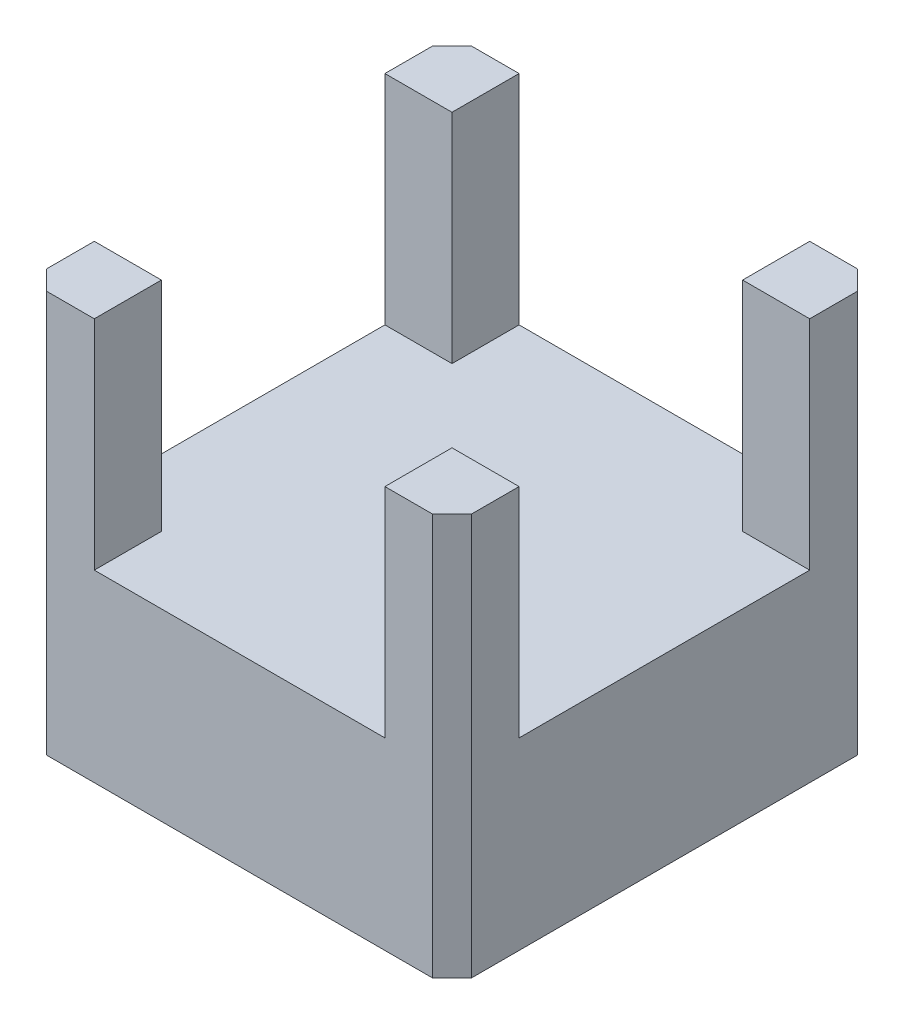
SolidWorks part; units mm, degrees
ref_plane "Front Plane" through (0, 0, 0) normal (0, 0, 1) x (1, 0, 0)
ref_plane "Top Plane" through (0, 0, 0) normal (0, 1, 0) x (1, 0, 0)
ref_plane "Right Plane" through (0, 0, 0) normal (1, 0, 0) x (0, 0, -1)
sketch "Sketch2" plane through (0, 0, 0) normal (0, 1, 0) x (1, 0, 0)
  line L0 (-21.875, 19.875) -> (-19.875, 21.875)
  line L1 (-19.875, 21.875) -> (19.875, 21.875)
  line L2 (-21.875, 19.875) -> (-21.875, -19.875)
  line L3 (-19.875, -21.875) -> (19.875, -21.875)
  line L4 (21.875, 19.875) -> (21.875, -19.875)
  line L5 (-21.875, 21.875) -> (21.875, -21.875) construction
  line L6 (-21.875, -21.875) -> (21.875, 21.875) construction
  line L7 (19.875, 21.875) -> (21.875, 19.875)
  line L8 (21.875, -19.875) -> (19.875, -21.875)
  line L9 (-21.875, -19.875) -> (-19.875, -21.875)
  point P0 (0, 0)
  dimension "D1" = 43.75
extrude "Boss-Extrude1" add sketch "Sketch2" along normal blind 41.38 contours L2 L9 L3 L8 L4 L7 L1 L0
sketch "Sketch3" plane through (0, 41.38, 0) normal (0, 1, 0) x (1, 0, 0)
  line L0 (-21.875, 19.875) -> (-21.875, -19.875) construction
  line L4 (-21.875, -14.965) -> (-21.875, 14.965)
  line L5 (21.875, 0) -> (-21.875, 0) construction
  line L7 (-19.875, 21.875) -> (19.875, 21.875) construction
  line L11 (14.965, 21.875) -> (-14.965, 21.875)
  line L13 (0, -21.875) -> (0, 21.875) construction
  line L14 (-22.759, 0) -> (22.759, 0) construction
  line L15 (0, -22.759) -> (0, 22.759) construction
  line L16 (14.965, 14.965) -> (21.875, 14.965)
  line L17 (14.965, 14.965) -> (14.965, 21.875)
  line L18 (-14.965, 14.965) -> (-14.965, 21.875)
  line L19 (-14.965, 14.965) -> (-21.875, 14.965)
  line L20 (21.875, -14.965) -> (21.875, 14.965)
  line L21 (-14.965, -14.965) -> (-21.875, -14.965)
  line L22 (-14.965, -14.965) -> (-14.965, -21.875)
  line L23 (14.965, -14.965) -> (14.965, -21.875)
  line L24 (14.965, -14.965) -> (21.875, -14.965)
  line L25 (14.965, -21.875) -> (-14.965, -21.875)
  point P0 (0, 0)
  point P10 (0, 0)
  point P25 (0, 0)
  dimension "D1" = 6.91
  dimension "D2" = 6.91
extrude "Cut-Extrude1" cut sketch "Sketch3" against normal blind 22.42 and the other way through all contours L20 L16 L17 L11 L18 L19 L4 L21 L22 L25 L23 L24
ref_axis "Axis1" through (0, -2.069, 0) along (0, 1, 0)
